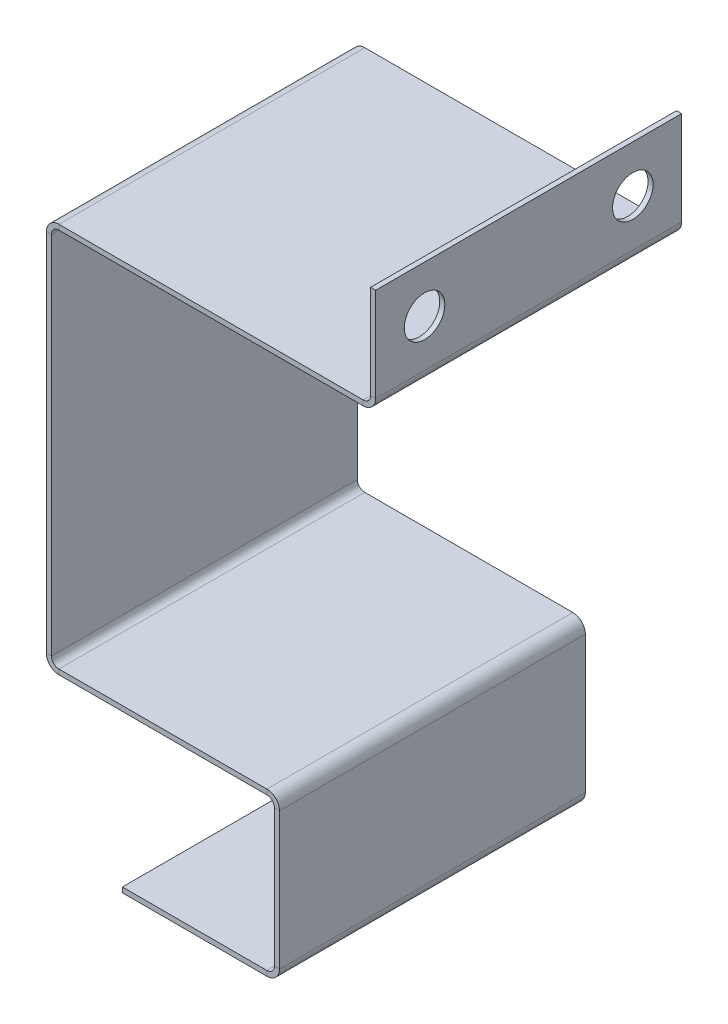
SolidWorks part; units mm, degrees
note: The reader was unsure of these and kept them because the rebuilt part matched: flange length of "Edge-Flange1", "Edge-Flange2", "Edge-Flange6", "Edge-Flange7", "Edge-Flange8".
ref_plane "Front Plane" through (0, 0, 0) normal (0, 0, 1) x (1, 0, 0)
ref_plane "Top Plane" through (0, 0, 0) normal (0, 1, 0) x (1, 0, 0)
ref_plane "Right Plane" through (0, 0, 0) normal (1, 0, 0) x (0, 0, -1)
sketch "Sketch1" plane through (0, 0, 0) normal (0, 1, 0) x (1, 0, 0)
  line L1 (-7.5, 15.0907) -> (7.5, 15.0907)
  line L2 (-7.5, 15.0907) -> (-7.5, -15.0907)
  line L3 (-7.5, -15.0907) -> (7.5, -15.0907)
  line L4 (7.5, 15.0907) -> (7.5, -15.0907)
  line L5 (-7.5, 15.0907) -> (7.5, -15.0907) construction
  line L6 (-7.5, -15.0907) -> (7.5, 15.0907) construction
  point P0 (0, 0)
base flange "Base-Flange2" sketch "Sketch1" thickness 0.5 reverse thickness direction yes parameters "D1"=0.7366
edge flange "Edge-Flange1" sketch "Sketch18" flange angle 90 flange length 15 flange position material outside bend radius 0.7366 thickness 0.5 relief rectangular parameters "D6"=10
sketch "Sketch18" plane through (7.5, 0.5, 0) normal (1, 0, 0) x (0, 0, -1)
  line L0 (-15.0907, 0) -> (15.0907, 0) construction
  line L1 (-15.0907, 0) -> (15.0907, 0)
  line L2 (-15.0907, 0) -> (-15.0907, 15)
  line L3 (-15.0907, 15) -> (15.0907, 15)
  line L4 (15.0907, 15) -> (15.0907, 0)
bend "EdgeBend1" bend radius 0.7366 bend angle 90 parameters "D5"=1
edge flange "Edge-Flange2" sketch "Sketch23" flange angle 90 flange length 22 flange position material outside bend radius 0.7366 thickness 0.5 relief rectangular parameters "D6"=10
sketch "Sketch23" plane through (7.5, 15.5, 0) normal (0, -1, 0) x (0, 0, 1)
  line L1 (15.0907, 0) -> (-15.0907, 0) construction
  line L2 (-15.0907, 0) -> (-15.0907, 22)
  line L3 (-15.0907, 22) -> (15.0907, 22)
  line L4 (15.0907, 22) -> (15.0907, 0)
  line L5 (15.0907, 0) -> (-15.0907, 0)
bend "EdgeBend2" bend radius 0.7366 bend angle 90 parameters "D5"=2
edge flange "Edge-Flange6" sketch "Sketch43" flange angle 90 flange length 37.5 flange position material outside bend radius 0.7366 thickness 0.5 relief rectangular parameters "D6"=10
sketch "Sketch43" plane through (-14.5, 16, 0) normal (1, 0, 0) x (0, 0, -1)
  line L1 (15.0907, 0) -> (-15.0907, 0) construction
  line L2 (-15.0907, 0) -> (-15.0907, 37.5)
  line L3 (-15.0907, 37.5) -> (15.0907, 37.5)
  line L4 (15.0907, 37.5) -> (15.0907, 0)
  line L5 (15.0907, 0) -> (-15.0907, 0)
bend "EdgeBend6" bend radius 0.7366 bend angle 90 parameters "D5"=3
edge flange "Edge-Flange7" sketch "Sketch48" flange angle 90 flange length 31.5 flange position material outside bend radius 0.7366 thickness 0.5 relief rectangular parameters "D6"=10
sketch "Sketch48" plane through (-14.5, 53.5, 0) normal (0, -1, 0) x (0, 0, -1)
  line L1 (15.0907, 0) -> (-15.0907, 0) construction
  line L2 (-15.0907, 0) -> (-15.0907, 31.5)
  line L3 (-15.0907, 31.5) -> (15.0907, 31.5)
  line L4 (15.0907, 31.5) -> (15.0907, 0)
  line L5 (15.0907, 0) -> (-15.0907, 0)
bend "EdgeBend7" bend radius 0.7366 bend angle 90 parameters "D5"=4
edge flange "Edge-Flange8" sketch "Sketch55" flange angle 90 flange length 10 flange position material outside bend radius 0.7366 thickness 0.5 relief rectangular parameters "D6"=10
sketch "Sketch55" plane through (17, 54, 0) normal (-1, 0, 0) x (0, 0, 1)
  line L1 (15.0907, 0) -> (-15.0907, 0) construction
  line L2 (-15.0907, 0) -> (-15.0907, 10)
  line L3 (-15.0907, 10) -> (15.0907, 10)
  line L4 (15.0907, 10) -> (15.0907, 0)
  line L5 (15.0907, 0) -> (-15.0907, 0)
bend "EdgeBend8" bend radius 0.7366 bend angle 90 parameters "D5"=5
sketch "Sketch58" plane through (17, 0, 0) normal (-1, 0, 0) x (0, 0, 1)
  line L0 (0, 64) -> (0, 74.0432) construction
  circle A0 centre (10.2762, 59.3683) radius 2
  circle A1 centre (-10.2762, 59.3683) radius 2
extrude "Cut-Extrude1" cut sketch "Sketch58" against normal through all normal cut yes
sketch "Bend-Lines3" plane through (0, 0, 0) normal (0, 1, 0) x (1, 0, 0)
sketch "Bounding-Box3" plane through (0, 0, 0) normal (0, 1, 0) x (1, 0, 0)
sheet metal parameters "Sheet-Metal(2)" thickness 0.5 parameters "D1"=0.7366
flat pattern "Flat-Pattern(2)" [suppressed]
sketch "Bend-Lines4" plane through (0, 0, 0) normal (0, 1, 0) x (1, 0, 0)
sketch "Bounding-Box4" [suppressed] plane through (0, 0, 0) normal (0, 1, 0) x (1, 0, 0)
sheet metal parameters "Sheet-Metal(3)" thickness 0.5 parameters "D1"=0.7366
flat pattern "Flat-Pattern(2)" [suppressed]
sketch "Bend-Lines5" plane through (0, 0, 0) normal (0, 1, 0) x (1, 0, 0)
sketch "Bounding-Box5" [suppressed] plane through (0, 0, 0) normal (0, 1, 0) x (1, 0, 0)
bend of the flat pattern "Flatten-<EdgeBend1>1"
sheet metal parameters "Sheet-Metal(4)" thickness 0.5 parameters "D1"=0.7366
flat pattern "Flat-Pattern(2)" [suppressed]
sketch "Bend-Lines6" plane through (0, 0, 0) normal (0, 1, 0) x (1, 0, 0)
sketch "Bounding-Box6" [suppressed] plane through (0, 0, 0) normal (0, 1, 0) x (1, 0, 0)
bend of the flat pattern "Flatten-<EdgeBend1>2"
bend of the flat pattern "Flatten-<EdgeBend2>1"
sheet metal parameters "Sheet-Metal(8)" thickness 0.5 parameters "D1"=0.7366
flat pattern "Flat-Pattern(2)" [suppressed]
sketch "Bend-Lines10" plane through (0, 0, 0) normal (0, 1, 0) x (1, 0, 0)
sketch "Bounding-Box10" [suppressed] plane through (0, 0, 0) normal (0, 1, 0) x (1, 0, 0)
bend of the flat pattern "Flatten-<EdgeBend1>6"
bend of the flat pattern "Flatten-<EdgeBend2>5"
bend of the flat pattern "Flatten-<EdgeBend6>1"
sheet metal parameters "Sheet-Metal(9)" thickness 0.5 parameters "D1"=0.7366
flat pattern "Flat-Pattern(2)" [suppressed]
sketch "Bend-Lines11" plane through (0, 0, 0) normal (0, 1, 0) x (1, 0, 0)
sketch "Bounding-Box11" [suppressed] plane through (0, 0, 0) normal (0, 1, 0) x (1, 0, 0)
bend of the flat pattern "Flatten-<EdgeBend1>7"
bend of the flat pattern "Flatten-<EdgeBend2>6"
bend of the flat pattern "Flatten-<EdgeBend6>2"
bend of the flat pattern "Flatten-<EdgeBend7>1"
sheet metal parameters "Sheet-Metal(10)" thickness 0.5 parameters "D1"=0.7366
flat pattern "Flat-Pattern(2)" [suppressed]
sketch "Bend-Lines12" plane through (0, 0, 0) normal (0, 1, 0) x (1, 0, 0)
sketch "Bounding-Box12" [suppressed] plane through (0, 0, 0) normal (0, 1, 0) x (1, 0, 0)
bend of the flat pattern "Flatten-<EdgeBend1>8"
bend of the flat pattern "Flatten-<EdgeBend2>7"
bend of the flat pattern "Flatten-<EdgeBend6>3"
bend of the flat pattern "Flatten-<EdgeBend7>2"
bend of the flat pattern "Flatten-<EdgeBend8>1"
sheet metal parameters "Sheet-Metal(11)" thickness 0.5 parameters "D1"=0.7366
flat pattern "Flat-Pattern(2)" [suppressed]
sketch "Bend-Lines13" plane through (0, 0, 0) normal (0, 1, 0) x (1, 0, 0)
sketch "Bounding-Box13" [suppressed] plane through (0, 0, 0) normal (0, 1, 0) x (1, 0, 0)
bend of the flat pattern "Flatten-<EdgeBend1>9"
bend of the flat pattern "Flatten-<EdgeBend2>8"
bend of the flat pattern "Flatten-<EdgeBend6>4"
bend of the flat pattern "Flatten-<EdgeBend7>3"
bend of the flat pattern "Flatten-<EdgeBend8>2"
